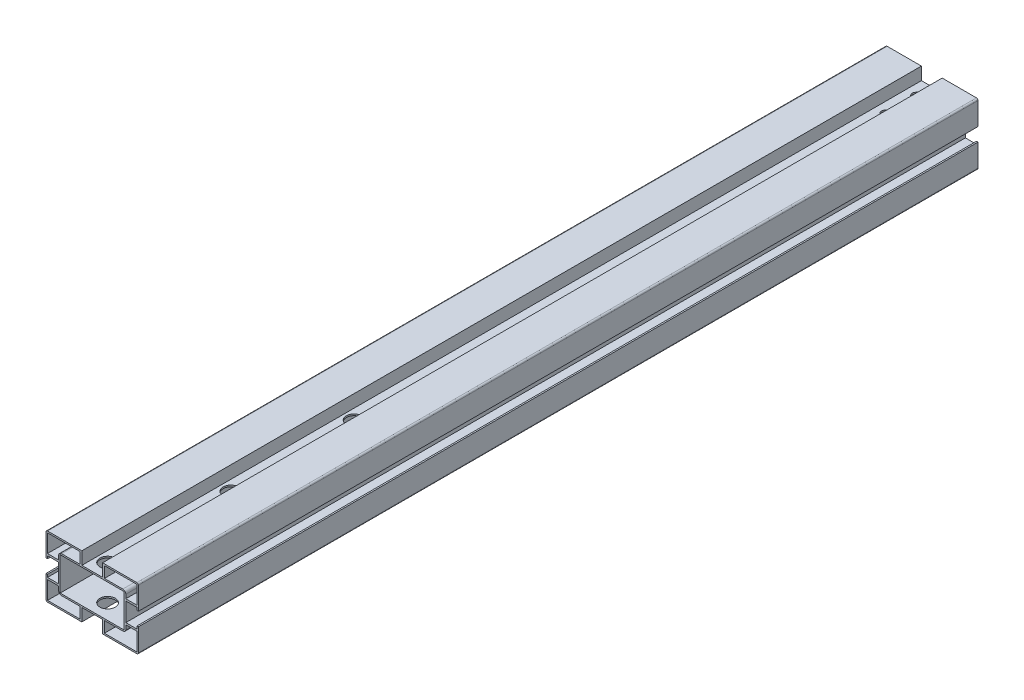
SolidWorks part; units mm, degrees
ref_plane "前视基准面" through (0, 0, 0) normal (0, 0, 1) x (1, 0, 0)
ref_plane "上视基准面" through (0, 0, 0) normal (0, 1, 0) x (1, 0, 0)
ref_plane "右视基准面" through (0, 0, 0) normal (1, 0, 0) x (0, 0, -1)
other "Configuration Table"
sketch "草图2" plane through (0, 0, 0) normal (0, 0, 1) x (1, 0, 0)
  line L0 (21.8177, 11.8) -> (7.9411, 11.8)
  line L1 (0, 10.8) -> (-20.8, 10.8)
  line L2 (-20.8, 10.8) -> (-20.8, -10.8)
  line L3 (-20.8, -10.8) -> (20.8, -10.8)
  line L4 (20.8, -10.8) -> (20.8, 10.8)
  line L5 (20.8, 10.8) -> (0, 10.8)
  line L7 (-21.8, 11.8) -> (-21.8, 7.3)
  line L8 (-21.8, -11.8) -> (-7.9411, -11.8)
  line L9 (21.8177, -11.8) -> (21.8177, -7.3)
  line L11 (0.0089, 11.8) -> (-6.7411, 11.8)
  line L12 (-6.7411, 11.8) -> (-6.7411, 19)
  line L14 (-7.9411, 11.8) -> (-7.9411, 19)
  line L15 (-28.9911, 19) -> (-7.9411, 19)
  line L16 (-6.7411, 19) -> (-6.7411, 20)
  line L17 (-6.7411, 20) -> (-29, 20)
  line L19 (-29, 20) -> (-29.9911, 20)
  line L20 (-29.9911, 20) -> (-29.9911, 19)
  line L22 (-21.8, -7.3) -> (-21.8, -11.8)
  line L23 (-6.7411, -11.8) -> (6.7411, -11.8)
  line L24 (7.9411, 11.8) -> (7.9411, 19)
  line L25 (6.7411, 11.8) -> (6.7411, 19)
  line L26 (6.7411, 19) -> (6.7411, 20)
  line L27 (28.9911, 19) -> (7.9411, 19)
  line L29 (29, 20) -> (29.9911, 20)
  line L30 (6.7411, 20) -> (29, 20)
  line L31 (29.9911, 20) -> (29.9911, 19)
  line L32 (-6.7411, -19) -> (-6.7411, -20)
  line L33 (-7.9411, -11.8) -> (-7.9411, -19)
  line L34 (-6.7411, -11.8) -> (-6.7411, -19)
  line L35 (-29.9911, -19) -> (-28.9911, -19)
  line L36 (-29, -20) -> (-29.9911, -20)
  line L37 (-29.9911, -20) -> (-29.9911, -19)
  line L38 (-28.9911, -19) -> (-7.9411, -19)
  line L39 (-6.7411, -20) -> (-29, -20)
  line L40 (7.9411, -11.8) -> (7.9411, -19)
  line L41 (6.7411, -11.8) -> (6.7411, -19)
  line L42 (6.7411, -19) -> (6.7411, -20)
  line L43 (29, -20) -> (29.9911, -20)
  line L45 (29.9911, -20) -> (29.9911, -19)
  line L46 (28.9911, -19) -> (7.9411, -19)
  line L47 (6.7411, -20) -> (29, -20)
  line L48 (-29.9911, 19) -> (-29.9911, 4.35)
  line L49 (-29.9911, 4.35) -> (-29.05, 4.35)
  line L50 (-29.05, 4.35) -> (-29.043, 6.1)
  line L51 (-29.043, 6.1) -> (-21.8, 6.1)
  line L52 (-29.0381, 7.3) -> (-21.8, 7.3)
  line L53 (-29.0381, 7.3) -> (-28.9911, 19)
  line L54 (-21.8, 6.1) -> (-21.8, -6.1)
  line L55 (-7.9411, 11.8) -> (-21.8, 11.8)
  line L56 (29.9911, 4.35) -> (29.05, 4.35)
  line L57 (29.05, 4.35) -> (29.043, 6.1)
  line L58 (29.043, 6.1) -> (21.8, 6.1)
  line L59 (29.0381, 7.3) -> (21.8, 7.3)
  line L60 (29.0381, 7.3) -> (28.9911, 19)
  line L61 (29.9911, 19) -> (29.9911, 4.35)
  line L62 (-29.0381, -7.3) -> (-28.9911, -19)
  line L63 (-29.9911, -19) -> (-29.9911, -4.35)
  line L64 (-29.9911, -4.35) -> (-29.05, -4.35)
  line L65 (-29.05, -4.35) -> (-29.043, -6.1)
  line L66 (-29.043, -6.1) -> (-21.8, -6.1)
  line L67 (-29.0381, -7.3) -> (-21.8, -7.3)
  line L68 (29.9911, -4.35) -> (29.05, -4.35)
  line L69 (29.05, -4.35) -> (29.043, -6.1)
  line L70 (29.043, -6.1) -> (21.8, -6.1)
  line L71 (29.0381, -7.3) -> (21.8, -7.3)
  line L72 (29.0381, -7.3) -> (28.9911, -19)
  line L73 (29.9911, -19) -> (29.9911, -4.35)
  line L74 (7.9411, -11.8) -> (21.8177, -11.8)
  line L75 (21.8177, -6.1) -> (21.8177, 6.1)
  line L76 (21.8177, 7.3) -> (21.8177, 11.8)
  line L77 (6.7411, 11.8) -> (-6.7411, 11.8)
  dimension "D1" = 41.6
  dimension "D2" = 21.6
  dimension "D3" = 1
  dimension "D4" = 6.75
  dimension "D5" = 7.2
  dimension "D6" = 1
  dimension "D7" = 30
  dimension "D8" = 1.2
  dimension "D9" = 15.65
  dimension "D10" = 13.9
  dimension "D11" = 1.2
extrude "凸台-拉伸1" add sketch "草图2" along normal blind 545 contours L25 L77 L11 L12 L16 L17 L19 L20 L48 L49 L50 L51 L54 L66 L65 L64 L63 L62 L67 L22 L8 L33 L38 L37 L36 L39 L32 L34 L23 L41 L42 L47 L43 L45 L73 L68 L69 L70 L75 L58 L57 L56 L61 L31 L29 region at (-29.2702, -11.675, 0)
fillet "圆角1" radius 1 4 edges at (29.9911, -20, 272.5) (-29.9911, 20, 272.5) (-29.9911, -20, 272.5) (29.9911, 20, 272.5)
fillet "圆角2" radius 1.95 4 edges at (-21.8, -11.8, 272.5) (21.8177, -11.8, 272.5) (21.8177, 11.8, 272.5) (-21.8, 11.8, 272.5)
sketch "草图3" plane through (0, 20, 0) normal (0, 1, 0) x (1, 0, 0)
  line L0 (0, 0) -> (0, -40)
  line L1 (6.7411, 0) -> (-6.7411, 0) construction
  line L2 (0, -20) -> (0, -10)
  line L3 (0, -20) -> (0, -30)
  line L4 (0, -545) -> (0, -535)
  line L5 (6.7411, -545) -> (-6.7411, -545) construction
  circle A0 centre (0, -10) radius 2.65
  circle A1 centre (0, -30) radius 2.65
  circle A2 centre (0, -535) radius 5
  circle A3 centre (0, -455) radius 5
  circle A4 centre (0, -375) radius 5
  circle A8 centre (0, -135) radius 5 [skipped]
  circle A9 centre (0, -215) radius 5 [skipped]
  circle A10 centre (0, -295) radius 5 [skipped]
  dimension "D4" = 6
  dimension "D1" = 40
  dimension "D2" = 10
  dimension "D3" = 20
  dimension "D5" = 10
extrude "切除-拉伸1" cut sketch "草图3" against normal through all contours L0 A0 | L0 A1 L3 | L3 A1 L0 | L0 A0 | A2 | A3 | A4
